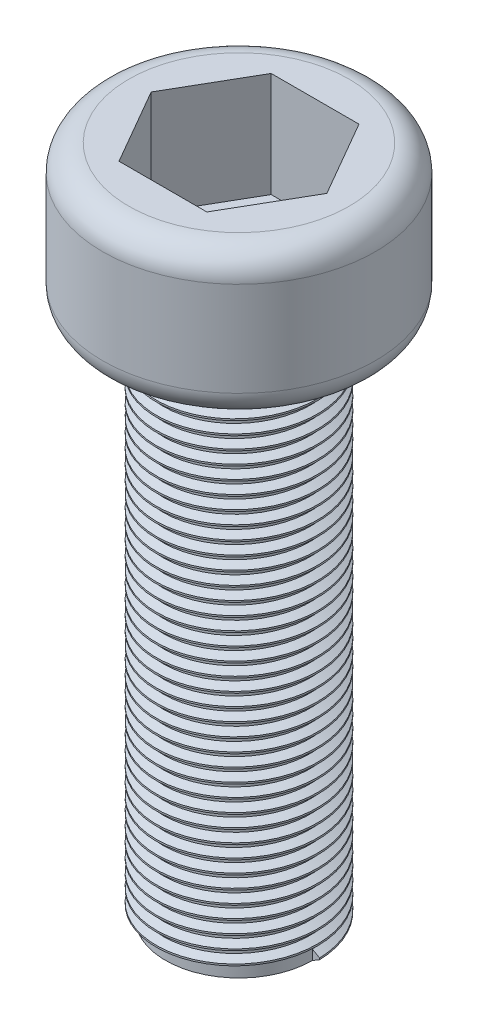
SolidWorks part; units mm, degrees
ref_plane "Alzado" through (0, 0, 0) normal (0, 0, 1) x (1, 0, 0)
ref_plane "Planta" through (0, 0, 0) normal (0, 1, 0) x (1, 0, 0)
ref_plane "Vista lateral" through (0, 0, 0) normal (1, 0, 0) x (0, 0, -1)
sketch "Croquis2" plane through (0, 0, 0) normal (1, 0, 0) x (0, 0, -1)
  line L0 (0, 6.4) -> (0, -6.4)
  line L1 (0, -6.4) -> (1.4, -6.4)
  line L2 (1.4, -6.4) -> (1.4, 3.6)
  line L3 (1.4, 3.6) -> (2.1, 3.6)
  line L4 (2.6, 4.1) -> (2.6, 5.9)
  line L5 (2.1, 6.4) -> (0, 6.4)
  line L6 (0, -6.4) -> (0, 6.4) construction
  arc A0 (2.6, 5.9) -> (2.1, 6.4) centre (2.1, 5.9) ccw
  arc A1 (2.6, 4.1) -> (2.1, 3.6) centre (2.1, 4.1) cw
  point P4 (0, 0)
  point P11 (2.6, 6.4)
  point P14 (2.6, 3.6)
  dimension "D5" = 0.5
  dimension "D1" = 1.4
  dimension "D2" = 2.6
  dimension "D3" = 12.8
  dimension "D4" = 2.8
revolve "Revolución1" add sketch "Croquis2" angle 360 about L6
sketch "Croquis3" plane through (0, 6.4, 0) normal (0, 1, 0) x (1, 0, 0)
  line L0 (0, 0) -> (0, 1.45) construction
  line L1 (1.6743, 0) -> (0.8372, 1.45)
  line L2 (0.8372, 1.45) -> (-0.8372, 1.45)
  line L3 (-0.8372, 1.45) -> (-1.6743, 0)
  line L4 (-1.6743, 0) -> (-0.8372, -1.45)
  line L5 (-0.8372, -1.45) -> (0.8372, -1.45)
  line L6 (0.8372, -1.45) -> (1.6743, 0)
  circle A0 centre (0, 0) radius 1.45 construction
  dimension "D1" = 2.9
extrude "Cortar-Extruir1" cut sketch "Croquis3" against normal blind 2
thread "Rosca1" pitch 0.25 method extrude profile "Perfil de rosca1" start angle 0, offset 0, length 9.8, pitch 0.25, diameter 2.8
ref_plane "Plano1" through (1.4, -6.4, 0) normal (0, 0, 1) x (1, 0, 0)
sketch "Perfil de rosca1" plane through (1.4, -6.4, 0) normal (0, 0, 1) x (1, 0, 0)
  line L0 (0, 0) -> (0, 0.25) construction
  line L1 (0, 0) -> (0.1353, 0.0781)
  line L2 (0.1353, 0.0781) -> (0.1353, 0.1094)
  line L3 (0.1353, 0.1094) -> (0, 0.1875)
  line L4 (0.1353, 0.0937) -> (0, 0.0937) construction
  line L11 (0, 0) -> (0, 0.1875)
  point P2 (0, 0)
  dimension "Pitch" = 0.25
  dimension "Profile_Angle" = 60
  dimension "Profile_Land" = 0.0312
  dimension "Profile_Height" = 0.1353
